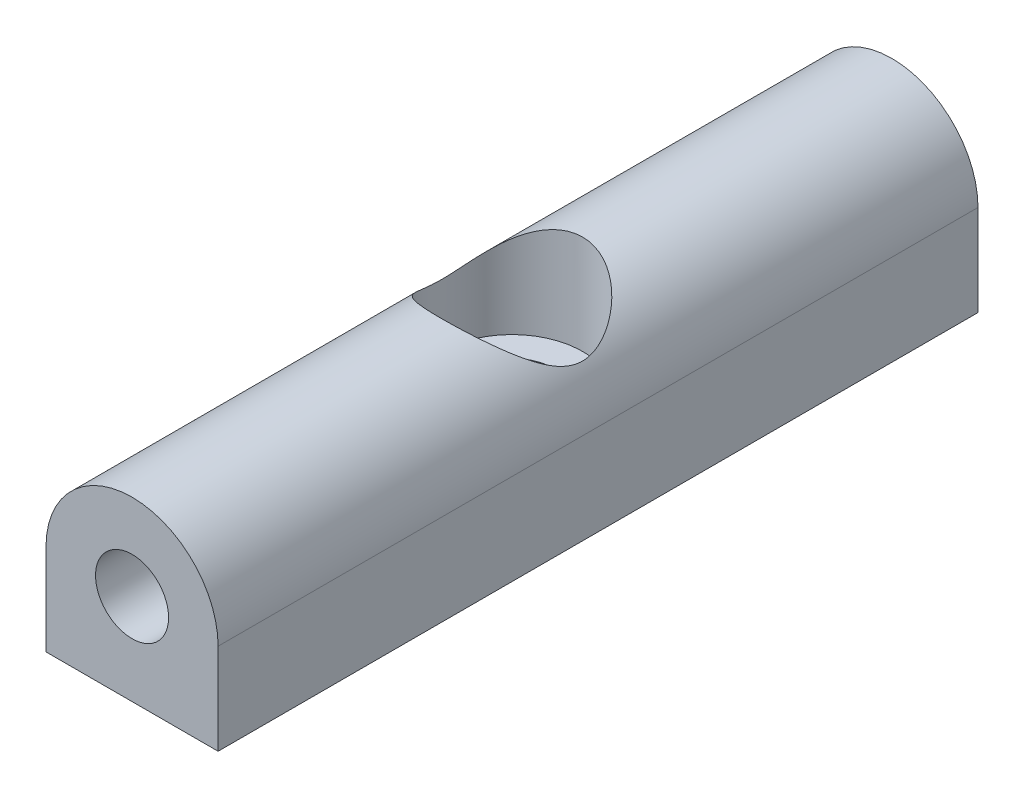
SolidWorks part; units mm, degrees
ref_plane "Front Plane" through (0, 0, 0) normal (0, 0, 1) x (1, 0, 0)
ref_plane "Top Plane" through (0, 0, 0) normal (0, 1, 0) x (1, 0, 0)
ref_plane "Right Plane" through (0, 0, 0) normal (1, 0, 0) x (0, 0, -1)
sketch "Sketch2" plane through (0, 0, 0) normal (0, 0, 1) x (1, 0, 0)
  circle A0 centre (0, 0) radius 1.475
  circle A1 centre (0, 0) radius 3.475
  dimension "D1" = 2.95
  dimension "D2" = 2
extrude "Boss-Extrude2" add sketch "Sketch2" along normal blind 30.6846 contours A1
sketch "Sketch3" plane through (0, 0, 30.6846) normal (0, 0, 1) x (1, 0, 0)
  circle A0 centre (0, 0) radius 1.475
  dimension "D1" = 2.95
extrude "Cut-Extrude1" cut sketch "Sketch3" against normal blind 10
sketch "Sketch4" plane through (0, 0, 0) normal (0, 0, -1) x (-1, 0, 0)
  circle A0 centre (0, 0) radius 1.475
  dimension "D1" = 2.95
extrude "Cut-Extrude2" cut sketch "Sketch4" against normal blind 10
sketch "Sketch5" plane through (0, 0, 0) normal (0, 0, -1) x (-1, 0, 0)
  line L0 (3.475, 0) -> (3.475, 1.469)
  line L2 (-3.475, 0) -> (3.475, 0)
  line L3 (-3.475, 0) -> (-3.475, -3.475)
  line L4 (-3.475, -3.475) -> (3.475, -3.475)
  line L5 (3.475, 0) -> (3.475, -3.475)
  circle A0 centre (0, 0) radius 3.475
  circle M7 centre (0, 0) radius 3.475
extrude "Boss-Extrude3" add sketch "Sketch5" against normal up to surface (30.6846 mm away) contours L3 L4 M7 | L5 L4 M7 up to face at (1.475, 0, 30.6846)
sketch "Sketch6" plane through (0, -3.475, 0) normal (0, -1, 0) x (1, 0, 0)
  line L1 (-3.475, 30.6846) -> (3.475, 30.6846)
  line L2 (-3.475, 30.6846) -> (-3.475, 0)
  line L3 (-3.475, 0) -> (3.475, 0)
  line L4 (3.475, 30.6846) -> (3.475, 0)
extrude "Boss-Extrude4" add sketch "Sketch6" along normal blind 0.2
sketch "Sketch8" plane through (-3.475, 0, 0) normal (-1, 0, 0) x (0, 0, 1)
  line L0 (15.3423, -3.675) -> (15.3423, 7.0199)
  line L1 (30.6846, -3.675) -> (0, -3.675) construction
  line L2 (30.6846, 3.475) -> (0, 3.475) construction
  line L3 (12.3423, 2.475) -> (18.3423, 2.475)
  line L4 (12.3423, 2.475) -> (12.3423, 4.475)
  line L5 (12.3423, 4.475) -> (18.3423, 4.475)
  line L6 (18.3423, 2.475) -> (18.3423, 4.475)
  line L7 (12.3423, 2.475) -> (18.3423, 4.475) construction
  line L8 (12.3423, 4.475) -> (18.3423, 2.475) construction
  point P4 (15.3423, 3.475)
  dimension "D1" = 6
  dimension "D2" = 2
extrude "Cut-Extrude3" cut sketch "Sketch8" against normal through all contours L3 L6 L5 L0 | L5 L4 L3 L0
sketch "Sketch10" plane through (0, 2.475, 0) normal (0, 1, 0) x (1, 0, 0)
  line L0 (-2.4393, -12.3423) -> (2.4393, -18.3423)
  circle A0 centre (0, -15.3423) radius 2.85
  line M2 (2.4393, -18.3423) -> (2.4393, -12.3423)
  line M4 (-2.4393, -12.3423) -> (-2.4393, -18.3423)
  dimension "D1" = 5.7
extrude "Cut-Extrude4" cut sketch "Sketch10" against normal blind 3 contours L0 A0 M2 | A0 M2 | L0 A0 M4 | A0 M4
sketch "Sketch11" plane through (0, -0.525, 0) normal (0, 1, 0) x (1, 0, 0)
  circle A0 centre (0, -15.3423) radius 1.675
  dimension "D1" = 3.35
extrude "Cut-Extrude5" cut sketch "Sketch11" against normal through all
sketch "Sketch12" plane through (0, 2.475, 0) normal (0, 1, 0) x (1, 0, 0)
  circle A0 centre (0, -15.3423) radius 2.85
  circle A1 centre (0, -15.3423) radius 4.85
  dimension "D1" = 2
extrude "Boss-Extrude5" add sketch "Sketch12" against normal up to surface (6.15 mm away) up to face at (0, -3.675, 17.0173)
sketch "Sketch13" plane through (0, 2.475, 0) normal (0, 1, 0) x (1, 0, 0)
  line L0 (2.4393, -11.1503) -> (2.4393, -12.3423)
  line L1 (2.4393, -12.3423) -> (2.4393, -11.1503) construction
  line L2 (2.4393, -12.3423) -> (-2.4393, -12.3423)
  line L3 (-2.4393, -12.3423) -> (-2.4393, -11.1503)
  line L4 (2.4393, -11.1503) -> (2.4393, -9.9584)
  line L5 (-2.4393, -18.3423) -> (-2.4393, -19.5343)
  line L6 (2.4393, -18.3423) -> (2.4393, -19.5343)
  line L7 (2.4393, -19.5343) -> (2.4393, -18.3423) construction
  line L8 (-2.4393, -19.5343) -> (-2.4393, -18.3423)
  line L9 (2.4393, -18.3423) -> (-2.4393, -18.3423)
  circle A0 centre (0, -15.3423) radius 2.85
  circle A1 centre (0, -15.3423) radius 4.85
  line M3 (-2.4393, -18.3423) -> (2.4393, -18.3423)
  line M4 (2.4393, -18.3423) -> (2.4393, -19.5343)
  arc M5 (2.4393, -19.5343) -> (2.4393, -11.1503) centre (0, -15.3423) ccw
  line M6 (2.4393, -11.1503) -> (2.4393, -12.3423)
  line M7 (2.4393, -12.3423) -> (-2.4393, -12.3423)
  line M8 (-2.4393, -12.3423) -> (-2.4393, -11.1503)
  arc M9 (-2.4393, -11.1503) -> (-2.4393, -19.5343) centre (0, -15.3423) ccw
  line M10 (-2.4393, -19.5343) -> (-2.4393, -18.3423)
  circle M11 centre (0, -15.3423) radius 2.85
extrude "Boss-Extrude7" add sketch "Sketch13" along normal up to vertex (1 mm away) contours M10 M3 M4 M5 M6 M7 M8 M9 M11
ref_plane "Plane1" through (3.475, -3.675, 0) normal (0, -1, 0) x (-1, 0, 0)
sketch "Sketch15" plane through (0, 0, 0) normal (0, 0, -1) x (-1, 0, 0)
  line L0 (-3.475, 0) -> (-8.1713, 0)
  line L1 (-8.1713, 0) -> (-8.1713, 6.0734)
  line L2 (-8.1713, 6.0734) -> (6.9757, 6.0734)
  line L3 (6.9757, 6.0734) -> (6.9757, 0)
  line L4 (6.9757, 0) -> (3.475, 0)
  circle A0 centre (0, 0) radius 3.475
  arc M2 (3.475, 0) -> (-3.475, 0) centre (0, 0) ccw
extrude "Cut-Extrude6" cut sketch "Sketch15" against normal through all contours L4 L3 L2 L1 L0 M2
sketch "Sketch16" plane through (0, -3.675, 0) normal (0, -1, 0) x (-1, 0, 0)
  line L0 (-3.475, -18.7256) -> (-3.475, -11.959)
  line L1 (-3.475, -11.959) -> (-9.4412, -13.4985)
  line L2 (-9.4412, -13.4985) -> (-7.4511, -19.0724)
  line L3 (-7.4511, -19.0724) -> (-3.475, -18.7256)
  line L4 (3.475, -18.7256) -> (3.475, -11.959)
  line L5 (3.475, -11.959) -> (8.5906, -11.959)
  line L6 (8.5906, -11.959) -> (7.5914, -18.7256)
  line L7 (7.5914, -18.7256) -> (3.475, -18.7256)
extrude "Cut-Extrude7" cut sketch "Sketch16" against normal through all
